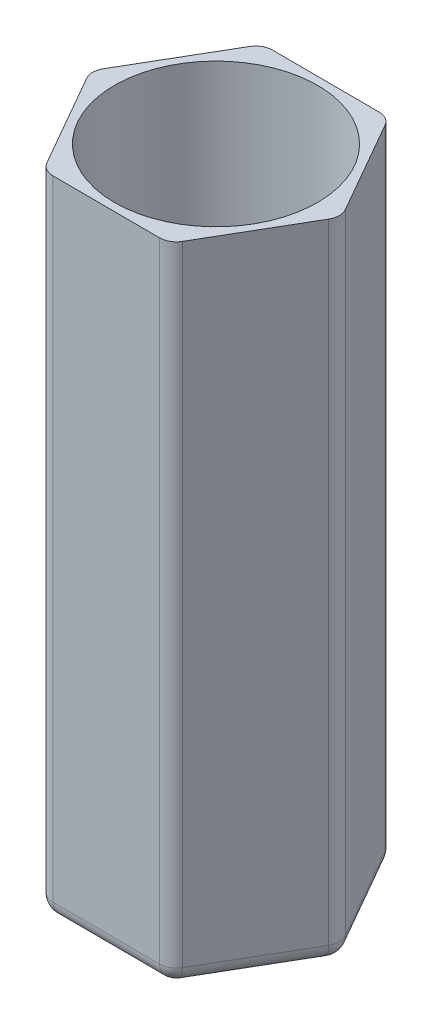
SolidWorks part; units mm, degrees
ref_plane "Front Plane" through (0, 0, 0) normal (0, 0, 1) x (1, 0, 0)
ref_plane "Top Plane" through (0, 0, 0) normal (0, 1, 0) x (1, 0, 0)
ref_plane "Right Plane" through (0, 0, 0) normal (1, 0, 0) x (0, 0, -1)
sketch "Sketch2" plane through (0, 0, 0) normal (0, 1, 0) x (1, 0, 0)
  line L1 (9.5622, -16.7041) -> (19.2473, -0.0709)
  line L2 (19.2473, -0.0709) -> (9.6851, 16.6332)
  line L3 (9.6851, 16.6332) -> (-9.5622, 16.7041)
  line L4 (-9.5622, 16.7041) -> (-19.2473, 0.0709)
  line L5 (-19.2473, 0.0709) -> (-9.6851, -16.6332)
  line L6 (-9.6851, -16.6332) -> (9.5622, -16.7041)
  circle A0 centre (0, 0) radius 16.6688 construction
  point P1 (-9.5622, -16.7041)
  dimension "D1" = 33.3375
extrude "Boss-Extrude1" add sketch "Sketch2" along normal blind 98.425
sketch "Sketch3" plane through (0, 98.425, 0) normal (0, 1, 0) x (1, 0, 0)
  circle A0 centre (0, 0) radius 15.4781
  dimension "D1" = 30.9562
extrude "Cut-Extrude1" cut sketch "Sketch3" against normal blind 85.725
fillet "Fillet1" radius 1.27 1 edges at (0, 12.7, 15.4781)
fillet "Fillet2" radius 2.54 6 edges at (14.4047, 0, 8.3875) (-0.0614, 0, 16.6686) (-14.4662, 0, 8.2811) (-14.4047, 0, -8.3875) (0.0614, 0, -16.6686) (14.4662, 0, -8.2811)
fillet "Fillet3" radius 2.54 12 edges at (9.2528, 0.7439, -15.8908) (-9.1354, 0.7439, -15.9586) (-18.3883, 0.7439, -0.0678) (-9.2528, 0.7439, 15.8908) (9.1354, 0.7439, 15.9586) (18.3883, 0.7439, 0.0678) (9.6851, 50.4825, -16.6332) (-9.5622, 50.4825, -16.7041) (-19.2473, 50.4825, -0.0709) (-9.6851, 50.4825, 16.6332) (9.5622, 50.4825, 16.7041) (19.2473, 50.4825, 0.0709)
ref_plane "Plane3" through (0, 0, 15.4781) normal (0, 0, 1) x (1, 0, 0)
sketch "Sketch7" plane through (0, 0, 15.4781) normal (0, 0, 1) x (1, 0, 0)
  line L0 (0, 0) -> (0, 95.25)
  circle A0 centre (0, 95.25) radius 1.5875
  dimension "D2" = 3.175
  dimension "D1" = 95.25
extrude "Boss-Extrude3" add sketch "Sketch7" against normal blind 3.175 and the other way blind 0.7937 contours A0 region at (1.0908, 94.1592, 15.4781)
sketch "Sketch8" plane through (0, 0, 12.3031) normal (0, 0, -1) x (-1, 0, 0)
  circle A0 centre (0, 95.25) radius 1.5875
extrude "Cut-Extrude2" cut sketch "Sketch8" against normal blind 0.635
fillet "Fillet4" radius 1.524 1 edges at (-1.5875, 95.25, 12.9381)
fillet "Fillet5" radius 0.254 1 edges at (0.3557, 96.7971, 15.474)
